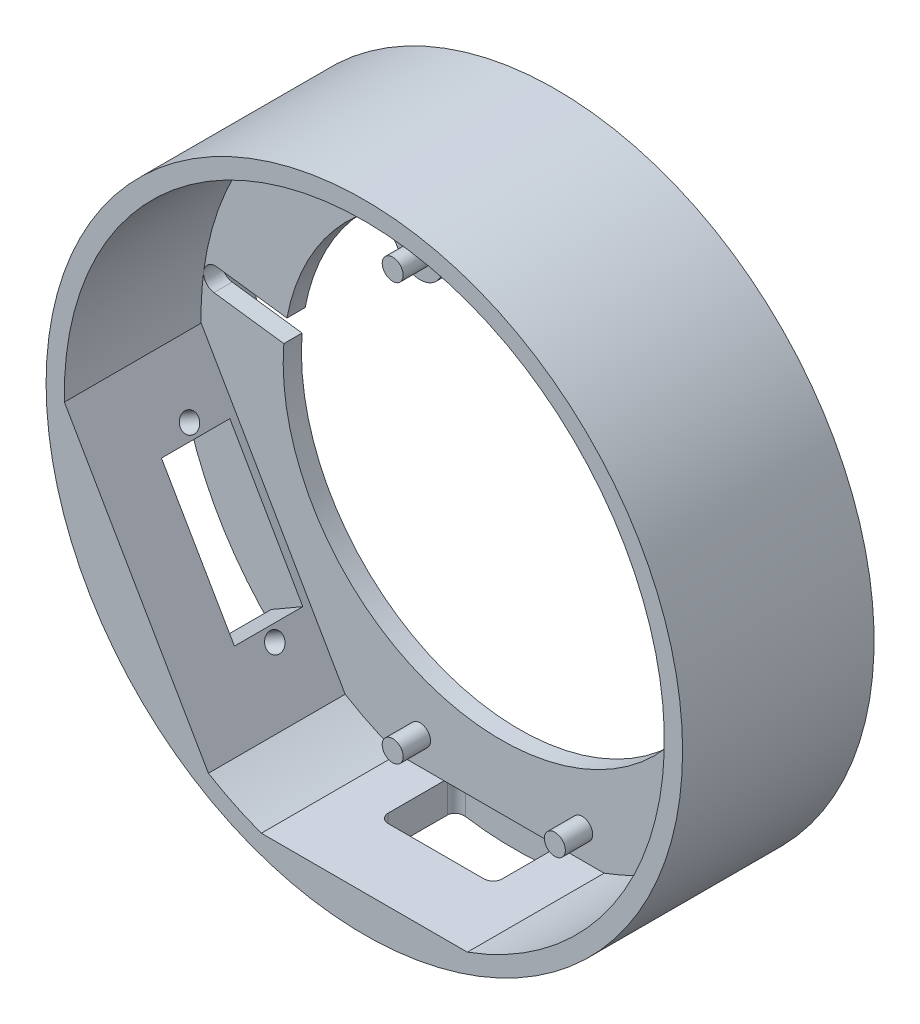
SolidWorks part; units mm, degrees
ref_plane "Plan de face" through (0, 0, 0) normal (0, 0, 1) x (1, 0, 0)
ref_plane "Plan de dessus" through (0, 0, 0) normal (0, 1, 0) x (1, 0, 0)
ref_plane "Plan de droite" through (0, 0, 0) normal (1, 0, 0) x (0, 0, -1)
sketch "Esquisse_carte_affichage" plane through (0, 0, 0) normal (0, 0, 1) x (1, 0, 0)
  circle A0 centre (19.25, 25.1) radius 0.5
  circle A1 centre (25.07, -19.23) radius 0.5
  circle A2 centre (29.18, 12.09) radius 0.5
  circle A3 centre (31.32, -4.14) radius 0.5
  circle A4 centre (-29.21, -12.07) radius 0.5
  circle A5 centre (-31.32, 4.14) radius 0.5
  circle A6 centre (-26.4935, -7.4094) radius 0.25
  circle A7 centre (-23.6728, -14.0139) radius 0.25
  circle A8 centre (-19.2392, -19.6637) radius 0.25
  circle A9 centre (-13.4943, -23.973) radius 0.25
  circle A10 centre (-6.8298, -26.6487) radius 0.25
  circle A11 centre (0.3, -27.5085) radius 0.25
  circle A12 centre (7.4094, -26.4935) radius 0.25
  circle A13 centre (14.0139, -23.6728) radius 0.25
  circle A14 centre (19.6637, -19.2392) radius 0.25
  circle A15 centre (23.973, -13.4943) radius 0.25
  circle A16 centre (26.6487, -6.8298) radius 0.25
  circle A17 centre (27.5085, 0.3) radius 0.25
  circle A18 centre (26.4935, 7.4094) radius 0.25
  circle A19 centre (23.6728, 14.0139) radius 0.25
  circle A20 centre (19.2392, 19.6637) radius 0.25
  circle A21 centre (13.4943, 23.973) radius 0.25
  circle A22 centre (6.8298, 26.6487) radius 0.25
  circle A23 centre (-0.3, 27.5085) radius 0.25
  circle A24 centre (-7.4094, 26.4935) radius 0.25
  circle A25 centre (-14.0139, 23.6728) radius 0.25
  circle A26 centre (-19.6637, 19.2392) radius 0.25
  circle A27 centre (-23.973, 13.4943) radius 0.25
  circle A28 centre (-26.6487, 6.8298) radius 0.25
  circle A29 centre (-27.5085, -0.3) radius 0.25
  circle A30 centre (-30.2, -7.1) radius 0.25
  circle A31 centre (-26.5986, -15.746) radius 0.25
  circle A32 centre (-28.1305, -7.8674) radius 0.25
  circle A33 centre (-21.6169, -22.0937) radius 0.25
  circle A34 centre (-25.1358, -14.8801) radius 0.25
  circle A35 centre (-15.162, -26.9359) radius 0.25
  circle A36 centre (-20.428, -20.8785) radius 0.25
  circle A37 centre (-7.6738, -29.9423) radius 0.25
  circle A38 centre (-14.3281, -25.4544) radius 0.25
  circle A39 centre (0.3371, -30.9082) radius 0.25
  circle A40 centre (-7.252, -28.2956) radius 0.25
  circle A41 centre (8.3254, -29.7678) radius 0.25
  circle A42 centre (0.3185, -29.2082) radius 0.25
  circle A43 centre (15.746, -26.5986) radius 0.25
  circle A44 centre (7.8674, -28.1305) radius 0.25
  circle A45 centre (22.0937, -21.6169) radius 0.25
  circle A46 centre (14.8801, -25.1358) radius 0.25
  circle A47 centre (26.9359, -15.162) radius 0.25
  circle A48 centre (20.8785, -20.428) radius 0.25
  circle A49 centre (29.9423, -7.6738) radius 0.25
  circle A50 centre (25.4544, -14.3281) radius 0.25
  circle A51 centre (30.9082, 0.3371) radius 0.25
  circle A52 centre (28.2956, -7.252) radius 0.25
  circle A53 centre (29.7678, 8.3254) radius 0.25
  circle A54 centre (29.2082, 0.3185) radius 0.25
  circle A55 centre (26.5986, 15.746) radius 0.25
  circle A56 centre (28.1305, 7.8674) radius 0.25
  circle A57 centre (21.6169, 22.0937) radius 0.25
  circle A58 centre (25.1358, 14.8801) radius 0.25
  circle A59 centre (15.162, 26.9359) radius 0.25
  circle A60 centre (20.428, 20.8785) radius 0.25
  circle A61 centre (7.6738, 29.9423) radius 0.25
  circle A62 centre (14.3281, 25.4544) radius 0.25
  circle A63 centre (-0.3371, 30.9082) radius 0.25
  circle A64 centre (7.252, 28.2956) radius 0.25
  circle A65 centre (-8.3254, 29.7678) radius 0.25
  circle A66 centre (-0.3185, 29.2082) radius 0.25
  circle A67 centre (-15.746, 26.5986) radius 0.25
  circle A68 centre (-7.8674, 28.1305) radius 0.25
  circle A69 centre (-22.0937, 21.6169) radius 0.25
  circle A70 centre (-14.8801, 25.1358) radius 0.25
  circle A71 centre (-26.9359, 15.162) radius 0.25
  circle A72 centre (-20.8785, 20.428) radius 0.25
  circle A73 centre (-29.9423, 7.6738) radius 0.25
  circle A74 centre (-25.4544, 14.3281) radius 0.25
  circle A75 centre (-30.9082, -0.3371) radius 0.25
  circle A76 centre (-28.2956, 7.252) radius 0.25
  circle A77 centre (0, 0) radius 26.162
  circle A78 centre (0, 0) radius 32.766
  dimension "D1" = 65.532
  dimension "D2" = 52.324
sketch "Esquisse_carte_mère" plane through (0, 0, 0) normal (0, 0, 1) x (1, 0, 0)
  line L0 (-11.3435, -28.5174) -> (-11.0897, -29.13)
  line L1 (-11.0897, -29.13) -> (-10.6861, -29.6561)
  line L2 (-10.6861, -29.6561) -> (-10.16, -30.0597)
  line L3 (-10.16, -30.0597) -> (-9.5474, -30.3135)
  line L4 (-9.5474, -30.3135) -> (-8.89, -30.4)
  line L5 (-8.89, -30.4) -> (-2.413, -30.4)
  line L6 (-2.413, -30.4) -> (-1.905, -29.892)
  line L7 (-1.905, -29.892) -> (1.905, -29.892)
  line L8 (1.905, -29.892) -> (2.413, -30.4)
  line L9 (2.413, -30.4) -> (8.89, -30.4)
  line L10 (8.89, -30.4) -> (9.5474, -30.3135)
  line L11 (9.5474, -30.3135) -> (10.16, -30.0597)
  line L12 (10.16, -30.0597) -> (10.6861, -29.6561)
  line L13 (10.6861, -29.6561) -> (11.0897, -29.13)
  line L14 (11.0897, -29.13) -> (11.3435, -28.5174)
  line L15 (11.3435, -28.5174) -> (11.43, -27.86)
  line L16 (11.43, -27.86) -> (11.43, 17.86)
  line L17 (11.43, 17.86) -> (11.3435, 18.5174)
  line L18 (11.3435, 18.5174) -> (11.0897, 19.13)
  line L19 (11.0897, 19.13) -> (10.6861, 19.6561)
  line L20 (10.6861, 19.6561) -> (10.16, 20.0597)
  line L21 (10.16, 20.0597) -> (9.5474, 20.3135)
  line L22 (9.5474, 20.3135) -> (8.89, 20.4)
  line L23 (8.89, 20.4) -> (-8.89, 20.4)
  line L24 (-8.89, 20.4) -> (-9.5474, 20.3135)
  line L25 (-9.5474, 20.3135) -> (-10.16, 20.0597)
  line L26 (-10.16, 20.0597) -> (-10.6861, 19.6561)
  line L27 (-10.6861, 19.6561) -> (-11.0897, 19.13)
  line L28 (-11.0897, 19.13) -> (-11.3435, 18.5174)
  line L29 (-11.3435, 18.5174) -> (-11.43, 17.86)
  line L30 (-11.43, 17.86) -> (-11.43, -27.86)
  line L31 (-11.43, -27.86) -> (-11.3435, -28.5174)
  line L32 (8.9522, -28.0199) -> (-18113.3609, 46572.2136) construction
  line L33 (-8.9266, -27.9541) -> (18113.3865, 46572.2795) construction
  circle A0 centre (-3.3, -25.05) radius 0.4
  circle A1 centre (3.3, -25.05) radius 0.4
  circle A2 centre (-3.6, -27.86) radius 0.45
  circle A3 centre (3.6, -27.86) radius 0.45
  circle A4 centre (10.16, 14.05) radius 0.5
  circle A5 centre (10.16, 11.51) radius 0.5
  circle A6 centre (10.16, 8.97) radius 0.5
  circle A7 centre (10.16, 6.43) radius 0.5
  circle A8 centre (10.16, 3.89) radius 0.5
  circle A9 centre (10.16, 1.35) radius 0.5
  circle A10 centre (10.16, -1.19) radius 0.5
  circle A11 centre (10.16, -3.73) radius 0.5
  circle A12 centre (10.16, -6.27) radius 0.5
  circle A13 centre (10.16, -8.81) radius 0.5
  circle A14 centre (10.16, -11.35) radius 0.5
  circle A15 centre (10.16, -13.89) radius 0.5
  circle A16 centre (-10.16, -24.05) radius 0.5
  circle A17 centre (-10.16, -21.51) radius 0.5
  circle A18 centre (-10.16, -18.97) radius 0.5
  circle A19 centre (-10.16, -16.43) radius 0.5
  circle A20 centre (-10.16, -13.89) radius 0.5
  circle A21 centre (-10.16, -11.35) radius 0.5
  circle A22 centre (-10.16, -8.81) radius 0.5
  circle A23 centre (-10.16, -6.27) radius 0.5
  circle A24 centre (-10.16, -3.73) radius 0.5
  circle A25 centre (-10.16, -1.19) radius 0.5
  circle A26 centre (-10.16, 1.35) radius 0.5
  circle A27 centre (-10.16, 3.89) radius 0.5
  circle A28 centre (-10.16, 6.43) radius 0.5
  circle A29 centre (-10.16, 8.97) radius 0.5
  circle A30 centre (-10.16, 11.51) radius 0.5
  circle A31 centre (-10.16, 14.05) radius 0.5
  circle A32 centre (-8.89, -27.86) radius 1.25
  circle A33 centre (8.89, -27.86) radius 1.25
  circle A34 centre (-8.89, 17.86) radius 1.25
  circle A35 centre (8.89, 17.86) radius 1.25
  circle A36 centre (-1.95, -25.955) radius 0.35
  circle A37 centre (1.95, -25.955) radius 0.35
  circle A38 centre (-2.2, 15.706) radius 0.45
  circle A39 centre (3.048, -15.795) radius 0.25
  circle A40 centre (1.016, -20.875) radius 0.25
  circle A41 centre (-6.223, -9.826) radius 0.25
  circle A42 centre (-6.096, -16.43) radius 0.25
  circle A43 centre (7.3914, -2.0028) radius 0.25
  circle A44 centre (7.366, -18.462) radius 0.25
  circle A45 centre (-1.905, 12.018) radius 0.25
  circle A46 centre (1.905, 9.224) radius 0.25
  circle A47 centre (-5.715, -21.129) radius 0.25
  circle A48 centre (-4.064, -1.571) radius 0.25
  circle A49 centre (-8.509, -22.78) radius 0.25
  circle A50 centre (0.2286, -14.5758) radius 0.25
  circle A51 centre (0.508, 7.446) radius 0.25
  circle A52 centre (0.635, 8.589) radius 0.25
  circle A53 centre (-7.112, 0.334) radius 0.25
  circle A54 centre (4.953, -15.795) radius 0.25
  circle A55 centre (0, 10.494) radius 0.25
  circle A56 centre (-4.191, -16.43) radius 0.25
  circle A57 centre (-0.889, -17.573) radius 0.25
  circle A58 centre (5.842, -10.715) radius 0.25
  circle A59 centre (2.159, -17.446) radius 0.25
  circle A60 centre (0, -27.987) radius 0.25
  circle A61 centre (-1.397, 4.271) radius 0.25
  circle A62 centre (-5.207, 1.985) radius 0.25
  circle A63 centre (-0.381, -6.651) radius 0.25
  circle A64 centre (6.858, 8.462) radius 0.25
  circle A65 centre (5.207, 3.128) radius 0.25
  circle A66 centre (2.667, 4.525) radius 0.25
  circle A67 centre (5.08, 11.764) radius 0.25
  circle A68 centre (0, 14.431) radius 0.25
  circle A69 centre (-1.778, 8.716) radius 0.25
  circle A70 centre (-2.921, 4.271) radius 0.25
  circle A71 centre (-5.588, 3.128) radius 0.25
  circle A72 centre (-1.905, -19.732) radius 0.25
  circle A73 centre (-5.842, -8.683) radius 0.25
  circle A74 centre (-3.048, -20.113) radius 0.25
  circle A75 centre (-6.604, -7.667) radius 0.25
  circle A76 centre (-5.207, -10.842) radius 0.25
  circle A77 centre (10.668, -26.082) radius 0.25
  circle A78 centre (5.969, -4.365) radius 0.25
  circle A79 centre (5.08, -9.191) radius 0.25
  circle A80 centre (-3.81, -3.349) radius 0.25
  circle A81 centre (-4.953, -9.699) radius 0.25
  circle A82 centre (3.048, 6.43) radius 0.25
  circle A83 centre (5.969, -3.222) radius 0.25
  circle A84 centre (6.858, -7.667) radius 0.25
  circle A85 centre (6.477, 6.303) radius 0.25
  circle A86 centre (-1.27, 10.367) radius 0.25
  circle A87 centre (-1.0922, -0.1994) radius 0.25
  circle A88 centre (0.508, -0.428) radius 0.25
  circle A89 centre (4.318, -17.065) radius 0.25
  circle A90 centre (1.524, 4.144) radius 0.25
  circle A91 centre (-2.921, -1.444) radius 0.25
  circle A92 centre (3.302, -10.08) radius 0.25
  circle A93 centre (-3.81, -10.08) radius 0.25
  circle A94 centre (-5.08, -6.778) radius 0.25
  point P222 (0, -5)
  dimension "D5" = 2.5
  dimension "D1" = 2.54
  dimension "D2" = 2.54
  dimension "D3" = 2.54
  dimension "D4" = 2.54
sketch "Esquisse_support" plane through (0, 0, 0) normal (0, 0, 1) x (1, 0, 0)
  line L0 (0, 0) -> (0, -50000) construction
  line L1 (0, 0) -> (-31.32, 4.14) construction
  line L2 (0, 0) -> (19.25, 25.1) construction
  line L3 (0, 0) -> (25.07, -19.23) construction
  line L4 (25.07, -19.23) -> (30456.2807, 39653.7005) construction
  line L5 (19.25, 25.1) -> (39694.4792, -30403.1136) construction
  line L6 (-31.32, 4.14) -> (6520.8813, 49572.9675) construction
  line L7 (-31.1487, 5.4363) -> (-23.4871, 4.4235)
  line L8 (-31.4913, 2.8437) -> (-23.8298, 1.831)
  line L9 (18.2437, 25.8718) -> (13.5179, 19.7098)
  line L10 (20.2563, 24.3282) -> (15.5305, 18.1663)
  line L11 (25.8637, -18.1952) -> (19.7291, -13.4897)
  line L12 (24.2763, -20.2648) -> (18.1417, -15.5592)
  line L13 (-8.89, 17.86) -> (46591.3436, 18140.1731) construction
  line L14 (8.89, 17.86) -> (-46591.3436, 18140.1731) construction
  line L15 (11.22, 16.9539) -> (13.5179, 19.7098)
  line L16 (72498.2044, -186428.9542) -> (-90602.6131, 232973.148) construction
  line L17 (-72498.1788, -186428.8884) -> (90602.6387, 232973.2138) construction
  circle A0 centre (0, 0) radius 32.9 construction
  circle A1 centre (0, 0) radius 34.9
  arc A2 (-32.6163, 4.3113) -> (-31.4913, 2.8437) centre (-31.32, 4.14) ccw
  arc A3 (-32.6163, 4.3113) -> (-31.1487, 5.4363) centre (-31.32, 4.14) cw
  arc A4 (20.0218, 26.1063) -> (18.2437, 25.8718) centre (19.25, 25.1) ccw
  arc A5 (20.0218, 26.1063) -> (20.2563, 24.3282) centre (19.25, 25.1) cw
  arc A6 (26.1048, -20.0237) -> (25.8637, -18.1952) centre (25.07, -19.23) ccw
  arc A7 (26.1048, -20.0237) -> (24.2763, -20.2648) centre (25.07, -19.23) cw
  arc A8 (-23.4871, 4.4235) -> (13.5179, 19.7098) centre (0, 0) cw construction
  arc A9 (-23.8298, 1.831) -> (18.1417, -15.5592) centre (0, 0) ccw
  arc A10 (19.7291, -13.4897) -> (15.5305, 18.1663) centre (0, 0) ccw
  arc A11 (-6.56, 18.7661) -> (-11.22, 16.9539) centre (-8.89, 17.86) cw
  arc A12 (6.56, 18.7661) -> (11.22, 16.9539) centre (8.89, 17.86) ccw
  arc A13 (-6.56, 18.7661) -> (-4.1838, 23.531) centre (-3.28, 20.1053) cw
  arc A14 (6.56, 18.7661) -> (4.1838, 23.531) centre (3.28, 20.1053) ccw
  arc A15 (-11.22, 16.9539) -> (-15.8818, 17.86) centre (-13.8724, 15.7529) ccw
  arc A16 (-23.4871, 4.4235) -> (-15.8818, 17.86) centre (0, 0) cw
  arc A17 (-4.1838, 23.531) -> (4.1838, 23.531) centre (0, 0) cw
  point P37 (-4.1838, 23.531)
  dimension "D1" = 65.8
  dimension "D2" = 69.8
  dimension "D12" = 2.5
  dimension "D13" = 2.5
  dimension "D3" = 90
  dimension "D4" = 90
  dimension "D5" = 90
  dimension "D7" = 90
  dimension "D8" = 90
  dimension "D9" = 90
  dimension "D10" = 90
  dimension "D11" = 90
extrude "Boss.-Extru.1" add sketch "Esquisse_support" along normal blind 2 contours A1 A13 A17 A14 A12 L15 L9 A4 A5 L10 A10 L11 A6 A7 L12 A9 L8 A2 A3 L7 A16 A15 A11 region at (-33.9129, 0, 0)
sketch "Esquisse6" plane through (0, 0, 2) normal (0, 0, 1) x (1, 0, 0)
  line L0 (0, 0) -> (0, -50000) construction
  circle A0 centre (-8.89, 17.86) radius 1.15
  circle A1 centre (-8.89, -27.86) radius 1.15
  circle A2 centre (8.89, -27.86) radius 1.15
  circle A3 centre (8.89, 17.86) radius 1.15
  dimension "D1" = 2.3
  dimension "D2" = 2.3
extrude "Boss.-Extru.2" add sketch "Esquisse6" along normal blind 3
sketch "Esquisse7" plane through (0, 0, 0) normal (0, 0, -1) x (-1, 0, 0)
  circle A0 centre (0, 0) radius 34.9
  circle A1 centre (0, 0) radius 32.9
extrude "Boss.-Extru.3" add sketch "Esquisse7" along normal blind 4
sketch "Esquisse8" plane through (0, 0, 2) normal (0, 0, 1) x (1, 0, 0)
  line L0 (0, 0) -> (0, -50000) construction
  line L1 (-11.296, -30.9) -> (11.296, -30.9)
  line L2 (-8.89, -30.4) -> (-2.413, -30.4) construction
  circle A0 centre (0, 0) radius 34.9
  circle A1 centre (0, 0) radius 32.9 construction
  arc A2 (-11.296, -30.9) -> (11.296, -30.9) centre (0, 0) cw
  point P9 (0, -30.9)
  point P16 (-25.8603, -16.6011)
  point P21 (-22.4942, -14.4402)
  circle M5 centre (0, 0) radius 34.9
  dimension "D2" = 0.5
extrude "Boss.-Extru.5" add sketch "Esquisse8" along normal blind 15 contours L1 M5 region at (-33.9129, 0, 2)
sketch "Ouverture_USB" plane through (0, -30.9, 0) normal (0, 1, 0) x (1, 0, 0)
  line L0 (0, -16.2747) -> (0, 5.3613) construction
  line L2 (-5.25, -9.13) -> (5.25, -9.13)
  line L3 (-6.25, -8.13) -> (-6.25, -1.63)
  line L4 (-5.25, -0.63) -> (5.25, -0.63)
  line L5 (6.25, -8.13) -> (6.25, -1.63)
  arc A0 (6.25, -8.13) -> (5.25, -9.13) centre (5.25, -8.13) cw
  arc A1 (6.25, -1.63) -> (5.25, -0.63) centre (5.25, -1.63) ccw
  arc A2 (-5.25, -0.63) -> (-6.25, -1.63) centre (-5.25, -1.63) ccw
  arc A3 (-6.25, -8.13) -> (-5.25, -9.13) centre (-5.25, -8.13) ccw
  dimension "D4" = 1
  dimension "D1" = 8.5
  dimension "D2" = 12.5
  dimension "D3" = 0.63
extrude "Enlèv. mat.-Extru.1" cut sketch "Ouverture_USB" against normal blind 10
sketch "Esquisse9" plane through (0, 0, 2) normal (0, 0, 1) x (1, 0, 0)
  line L0 (0, -1000) -> (0, 49000) construction
  line L1 (0, 0) -> (-43301.2702, -25000) construction
  line L2 (-34.3348, -6.2555) -> (-22.5848, -26.6071) construction
  line L3 (-32.8913, -0.7557) -> (-17.1001, -28.1069)
  arc A0 (-32.6163, 4.3113) -> (-11.296, -30.9) centre (0, 0) ccw construction
  arc A1 (-32.8913, -0.7557) -> (-17.1001, -28.1069) centre (0, 0) ccw
  circle A2 centre (0, 0) radius 34.9 construction
  point P11 (-28.4598, -16.4313)
  point P14 (-24.9957, -14.4313)
  arc M10 (-32.6163, 4.3113) -> (-11.296, -30.9) centre (0, 0) ccw
  dimension "D1" = 60
  dimension "D2" = 23.5
  dimension "D4" = 4
extrude "Boss.-Extru.6" add sketch "Esquisse9" along direction (0, 0, 1) on the side of the normal through all contours L3 M10 region at (-26.4019, -15.2432, 2)
sketch "Esquisse10" plane through (-24.9957, -14.4313, 0) normal (0.866, 0.5, 0) x (0, 0, -1)
  line L1 (-6.5, -15.7912) -> (-6.5, 15.7912) construction
  line L2 (-2.75, -8) -> (-10.25, -8)
  line L3 (-2.75, -8) -> (-2.75, 8)
  line L4 (-2.75, 8) -> (-10.25, 8)
  line L5 (-10.25, -8) -> (-10.25, 8)
  line L6 (-2.75, -8) -> (-10.25, 8) construction
  line L7 (-2.75, 8) -> (-10.25, -8) construction
  line L9 (-2.75, 0) -> (-10.25, 0) construction
  line L11 (-17, -15.7912) -> (-2, -15.7912) construction
  circle A0 centre (-6.5, -9.35) radius 1
  circle A1 centre (-6.5, 9.35) radius 1
  point P4 (-6.5, 0)
  point P14 (-6.5, 0)
  point P19 (-6.5, 0)
  point P21 (-6.5, 0)
  dimension "D3" = 9.35
  dimension "D4" = 2
  dimension "D1" = 16
  dimension "D2" = 7.5
extrude "Enlèv. mat.-Extru.2" cut sketch "Esquisse10" against normal through all
sketch "Esquisse12" plane through (-4, 6.9282, 0) normal (0.5, -0.866, 0) x (0.866, 0.5, 0)
  line L0 (-28.8626, 2.75) -> (-28.8626, 10.25) construction
  line L1 (-32.8626, 10.25) -> (-37.8626, 10.25)
  line L2 (-32.8626, 10.25) -> (-32.8626, 2.75)
  line L3 (-32.8626, 2.75) -> (-37.8626, 2.75)
  line L4 (-37.8626, 10.25) -> (-37.8626, 2.75)
  line L5 (-33.9707, 10.25) -> (-28.8626, 10.25) construction
  line L6 (-33.9707, 2.75) -> (-28.8626, 2.75) construction
  dimension "D1" = 4
  dimension "D2" = 5
extrude "Enlèv. mat.-Extru.3" cut sketch "Esquisse12" against normal through all both and the other way through all
